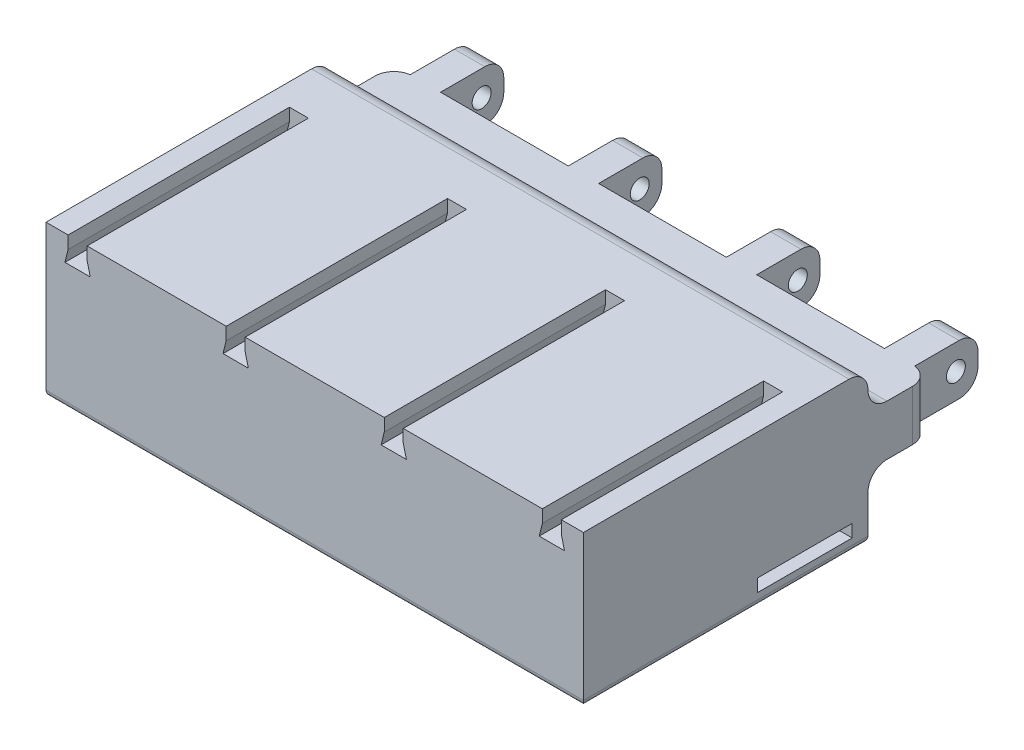
SolidWorks part; units mm, degrees
ref_plane "Alzado" through (0, 0, 0) normal (0, 0, 1) x (1, 0, 0)
ref_plane "Planta" through (0, 0, 0) normal (0, 1, 0) x (1, 0, 0)
ref_plane "Vista lateral" through (0, 0, 0) normal (1, 0, 0) x (0, 0, -1)
sketch "Croquis1" plane through (0, 0, 0) normal (1, 0, 0) x (0, 0, -1)
  line L0 (0, 9) -> (0, 1) construction
  line L9 (-1.5, 9) -> (-66.5, 9) construction
  line L18 (0, 9) -> (0, -9) construction
  line L19 (0, -9) -> (-66.5, -9) construction
  line L25 (0, 1) -> (-21.5, 1) construction
  line L26 (0, 1) -> (0, -2.6179) construction
  line L29 (0, -2.6179) -> (0, -9) construction
  line L31 (-1.5, 9) -> (-1.5, 1)
  line L32 (-21.5, 1) -> (-1.5, 1)
  line L35 (-66.5, -9) -> (-21.5, -9)
  line L56 (-66.5, 9) -> (-66.5, -9)
  line L59 (0, 9) -> (-66.5, 9) construction
  line L61 (-21.5, 1) -> (-21.5, -9)
  line L62 (-21.5, 9) -> (-21.5, 15)
  line L63 (-21.5, 15) -> (-66.5, 15)
  line L64 (-66.5, 15) -> (-66.5, 9)
  line L65 (-1.5, 9) -> (-21.5, 9)
  circle A0 centre (-5, 5) radius 1.5
  point P9 (0, 0)
  point P12 (0, 5)
  dimension "D6" = 3
  dimension "D1" = 20
  dimension "D2" = 10
  dimension "D3" = 45
  dimension "D4" = 8
  dimension "D5" = 6
  dimension "D7" = 5
  dimension "D8" = 3
extrude "Saliente-Extruir1" add sketch "Croquis1" along normal mid plane 85
sketch "Croquis2" plane through (0, 0, 0) normal (0, 1, 0) x (1, 0, 0)
  line L17 (42.5, -1.5) -> (-42.5, -1.5) construction
  line L18 (-39.9, -1.5) -> (-35.1, -1.5) construction
  line L19 (-39.9, -1.5) -> (-39.9, -11.5)
  line L20 (-39.9, -11.5) -> (-35.1, -11.5) construction
  line L21 (-35.1, -1.5) -> (-35.1, -11.5)
  line L23 (-14.9, -1.5) -> (-10.1, -1.5) construction
  line L24 (-14.9, -1.5) -> (-14.9, -11.5)
  line L25 (-14.9, -11.5) -> (-10.1, -11.5) construction
  line L26 (-10.1, -1.5) -> (-10.1, -11.5)
  line L27 (10.1, -1.5) -> (14.9, -1.5) construction
  line L28 (10.1, -1.5) -> (10.1, -11.5)
  line L29 (10.1, -11.5) -> (14.9, -11.5) construction
  line L30 (14.9, -1.5) -> (14.9, -11.5)
  line L31 (35.1, -1.5) -> (39.9, -1.5) construction
  line L32 (35.1, -1.5) -> (35.1, -11.5)
  line L33 (35.1, -11.5) -> (39.9, -11.5) construction
  line L34 (39.9, -1.5) -> (39.9, -11.5)
  line L39 (-39.9, -6.5) -> (39.9, -6.5) construction
  line L40 (14.9, -1.5) -> (35.1, -1.5)
  line L41 (14.9, -11.5) -> (35.1, -11.5)
  line L42 (-10.1, -1.5) -> (10.1, -1.5)
  line L43 (-10.1, -11.5) -> (10.1, -11.5)
  line L44 (-35.1, -11.5) -> (-14.9, -11.5)
  line L45 (-35.1, -1.5) -> (-14.9, -1.5)
  line L46 (-39.9, -1.5) -> (-42.5, -1.5)
  line L47 (-42.5, -1.5) -> (-42.5, -11.5)
  line L48 (-42.5, -11.5) -> (-39.9, -11.5)
  line L49 (39.9, -1.5) -> (42.5, -1.5)
  line L50 (42.5, -1.5) -> (42.5, -11.5)
  line L51 (42.5, -11.5) -> (39.9, -11.5)
  point P23 (-37.5, -11.5)
  point P24 (-12.5, -11.5)
  point P25 (12.5, -11.5)
  point P26 (37.5, -11.5)
  point P29 (0, -6.5)
  dimension "D1" = 4.8
  dimension "D2" = 25
  dimension "D3" = 25
  dimension "D4" = 25
  dimension "D5" = 10
extrude "Cortar-Extruir1" cut sketch "Croquis2" against normal through all both and the other way through all
sketch "Croquis4" plane through (0, 0, 0) normal (1, 0, 0) x (0, 0, -1)
  line L5 (-66.5, -9) -> (-21.5, -9) construction
  line L7 (-21.5, -9) -> (-21.5, 1) construction
  line L8 (-39, -5) -> (-24, -5)
  line L9 (-39, -5) -> (-39, -7)
  line L10 (-39, -7) -> (-24, -7)
  line L11 (-24, -5) -> (-24, -7)
  point P7 (-31.5, -7)
  dimension "D1" = 2
  dimension "D2" = 2
  dimension "D3" = 15
  dimension "D4" = 10
extrude "Cortar-Extruir4" cut sketch "Croquis4" against normal through all both and the other way through all
fillet "Redondeo3" radius 3 13 edges at (-37.5, 9, 1.5) (-37.5, 1, 1.5) (37.5, 9, 1.5) (37.5, 1, 1.5) (12.5, 9, 1.5) (12.5, 1, 1.5) (-12.5, 9, 1.5) (-12.5, 1, 1.5) (0, 1, 21.5) (0, 9, 21.5) (42.5, 5, 11.5) (-42.5, 5, 11.5) (0, 15, 21.5)
sketch "Croquis5" plane through (0, 0, 66.5) normal (0, 0, -1) x (-1, 0, 0)
  line L0 (10.1, 9) -> (14.9, 9) construction
  line L21 (37.5, 9) -> (37.5, 15) construction
  line L22 (35.1, 9) -> (39.9, 9) construction
  line L23 (-12.5, 9) -> (-12.5, 15) construction
  line L24 (-14.9, 9) -> (-10.1, 9) construction
  line L25 (-37.5, 9) -> (-37.5, 15) construction
  line L26 (-39.9, 9) -> (-35.1, 9) construction
  line L27 (12.5, 9) -> (12.5, 15) construction
  line L28 (11, 13) -> (10.5, 11)
  line L29 (11, 15) -> (14, 15)
  line L30 (11, 15) -> (11, 13)
  line L31 (11, 13) -> (14, 13) construction
  line L32 (14, 15) -> (14, 13)
  line L33 (10.5, 11) -> (14.5, 11)
  line L34 (14.5, 11) -> (14, 13)
  line L35 (-39, 13) -> (-39.5, 11)
  line L36 (36, 15) -> (39, 15)
  line L37 (36, 15) -> (36, 13)
  line L38 (36, 13) -> (39, 13) construction
  line L39 (39, 15) -> (39, 13)
  line L40 (-36, 15) -> (-39, 15)
  line L41 (-36, 15) -> (-36, 13)
  line L42 (-36, 13) -> (-39, 13) construction
  line L43 (-39, 15) -> (-39, 13)
  line L44 (-11, 15) -> (-14, 15)
  line L45 (-11, 15) -> (-11, 13)
  line L46 (-11, 13) -> (-14, 13) construction
  line L47 (-14, 15) -> (-14, 13)
  line L48 (-39.5, 11) -> (-35.5, 11)
  line L49 (-35.5, 11) -> (-36, 13)
  line L50 (-14, 13) -> (-14.5, 11)
  line L51 (-14.5, 11) -> (-10.5, 11)
  line L52 (-10.5, 11) -> (-11, 13)
  line L53 (36, 13) -> (35.5, 11)
  line L54 (35.5, 11) -> (39.5, 11)
  line L55 (39.5, 11) -> (39, 13)
  line L56 (-42.5, 15) -> (42.5, 15) construction
  point P12 (12.5, 15)
  point P30 (37.5, 15)
  point P39 (-12.5, 15)
  point P40 (-37.5, 15)
  dimension "D1" = 3
  dimension "D2" = 2
  dimension "D3" = 2
  dimension "D4" = 4
  dimension "D5" = 2
  dimension "D8" = 2
  dimension "D9" = 2
extrude "Cortar-Extruir6" cut sketch "Croquis5" along normal blind 35
fillet "Redondeo2" radius 1 4 edges at (42.5, -9, 44) (-42.5, -9, 44) (0, -9, 66.5) (0, -9, 21.5)
